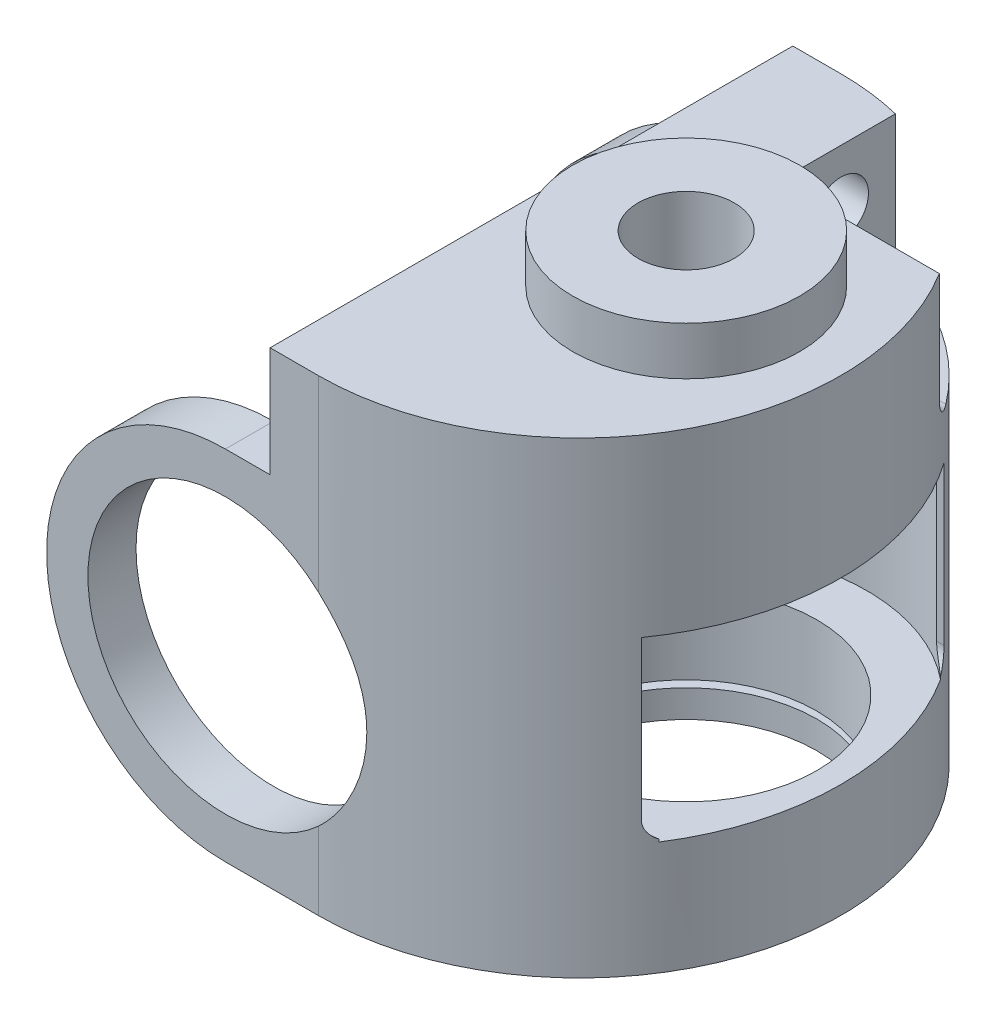
SolidWorks part; units mm, degrees
ref_plane "Plan de face" through (0, 0, 0) normal (0, 0, 1) x (1, 0, 0)
ref_plane "Plan de dessus" through (0, 0, 0) normal (0, 1, 0) x (1, 0, 0)
ref_plane "Plan de droite" through (0, 0, 0) normal (1, 0, 0) x (0, 0, -1)
sketch "Sketch2" plane through (0, 0, 0) normal (0, 1, 0) x (1, 0, 0)
  line L0 (-3.5, -19) -> (-3.5, 19)
  line L1 (-3.5, 19) -> (0, 19)
  line L2 (-3.5, -19) -> (0, -19)
  line L3 (19, 0) -> (19, 16.5672) construction
  arc A0 (0, -19) -> (0, 19) centre (0, 0) ccw
  circle A1 centre (7.75, 0) radius 3.5
  point P7 (-3.5, 0)
  dimension "D1" = 19
  dimension "D3" = 22.5
  dimension "D4" = 11.25
  dimension "D5" = 7
  dimension "D2" = 38
extrude "Boss-Extrude1" add sketch "Sketch2" along normal blind 34
sketch "Sketch19" plane through (0, 34, 0) normal (0, 1, 0) x (1, 0, 0)
  circle A0 centre (7.75, 0) radius 8.25
  circle A1 centre (7.75, 0) radius 3.5
  dimension "D1" = 16.5
  dimension "D2" = 7
extrude "Boss-Extrude3" add sketch "Sketch19" along normal blind 3.5
sketch "Sketch3" plane through (0, 0, 19) normal (0, 0, 1) x (1, 0, 0)
  line L3 (-3.5, 0) -> (-6.75, 0)
  line L4 (-6.75, 26) -> (-3.5, 26)
  line L5 (-3.5, 34) -> (-3.5, 0) construction
  arc A0 (-6.75, 26) -> (-6.75, 0) centre (-6.75, 13) ccw
  line M4 (-3.5, 34) -> (-3.5, 0)
  dimension "D1" = 26
  dimension "D2" = 3.25
extrude "Boss-Extrude2" add sketch "Sketch3" against normal blind 3.5 contours A0 M4 region at (-10.5428, 13, 19)
sketch "Sketch4" plane through (0, 0, 19) normal (0, 0, 1) x (1, 0, 0)
  circle A0 centre (-6.75, 13) radius 10
  dimension "D1" = 20
extrude "Cut-Extrude1" cut sketch "Sketch4" against normal up to surface (3.5 mm away) up to face at (-8.375, 13, 15.5)
pattern_linear "LPattern4" count 2 spacing 34.5 along (0, 0, -1) of "Boss-Extrude2", "Cut-Extrude1"
sketch "Sketch6" plane through (-3.5, 0, 0) normal (1, 0, 0) x (0, 0, -1)
  line L0 (15.5, 0) -> (-15.5, 0) construction
  line L1 (11, 21.25) -> (-11, 21.25)
  line L2 (11, 21.25) -> (11, 9.75)
  line L3 (9.5, 8.25) -> (-9.5, 8.25)
  line L4 (-11, 21.25) -> (-11, 9.75)
  arc A0 (-11, 9.75) -> (-9.5, 8.25) centre (-9.5, 9.75) ccw
  arc A1 (11, 9.75) -> (9.5, 8.25) centre (9.5, 9.75) cw
  point P6 (0, 8.25)
  point P10 (-11, 8.25)
  point P13 (11, 8.25)
  dimension "D4" = 1.5
  dimension "D1" = 8.25
  dimension "D2" = 22
  dimension "D3" = 13
extrude "Cut-Extrude3" cut sketch "Sketch6" along normal through all
sketch "Sketch7" plane through (0, 0, 15.5) normal (0, 0, -1) x (-1, 0, 0)
  circle A3 centre (6.75, 13) radius 13.5
  dimension "D3" = 27
extrude "Cut-Extrude4" cut sketch "Sketch7" along normal blind 4.5 contours A3
pattern_linear "LPattern3" count 2 spacing 26.5 along (0, 0, -1) of "Cut-Extrude4"
sketch "Sketch16" plane through (-3.5, 0, 0) normal (-1, 0, 0) x (0, 0, 1)
  line L0 (19, 34) -> (19, 26) construction
  line L1 (-19, 34) -> (19, 34) construction
  point P0 (11, 31.5)
  dimension "D1" = 8
  dimension "D2" = 2.5
hole_wizard "M2 Tapped Hole1" positions "Sketch16" profile "Sketch15" tap size "M2" standard "ISO"
sketch "Sketch15" plane through (-3.5, 31.5, 11) normal (0, 1, 0) x (0, 0, 1)
  line L0 (0, 0) -> (0, 5.9807)
  line L1 (0, 5.9807) -> (0.8, 5.5)
  line L2 (0.8, 5.5) -> (0.8, 0)
  line L5 (0.8, 0) -> (0, 0)
  line L10 (0, 5.9807) -> (-0.8, 5.5) construction
  line L11 (0, -6.35) -> (0, 107.95) construction
  dimension "Tap Drill Dia." = 1.6
  dimension "Tap Drill Depth" = 5.5
  dimension "Drill Angle" = 118
cosmetic thread "Hole Thread1" parameters "D1"=4.5, "D2"=2
sketch "Sketch17" plane through (-3.5, 0, 0) normal (-1, 0, 0) x (0, 0, 1)
  line L0 (-19, 34) -> (-19, 26) construction
  line L1 (-19, 34) -> (19, 34) construction
  circle A1 centre (-14.5, 30) radius 2
  dimension "D1" = 4
  dimension "D2" = 4.5
  dimension "D3" = 4
extrude "Cut-Extrude5" cut sketch "Sketch17" against normal blind 8
sketch "Sketch18" plane through (4.5, 0, 0) normal (-1, 0, 0) x (0, 0, 1)
  line L0 (-19, 34) -> (-19, 26) construction
  line L1 (-19, 24.5) -> (-11.5, 24.5)
  line L2 (-19, 24.5) -> (-19, 34)
  line L3 (-19, 34) -> (-10, 34)
  line L4 (-10, 26) -> (-10, 34)
  line L5 (-19, 34) -> (19, 34) construction
  arc A2 (-10, 26) -> (-11.5, 24.5) centre (-11.5, 26) cw
  dimension "D1" = 9.5
  dimension "D2" = 9
  dimension "D3" = 1.5
extrude "Cut-Extrude6" cut sketch "Sketch18" against normal up to next
sketch "Sketch20" plane through (0, 21.25, 0) normal (0, -1, 0) x (1, 0, 0)
  circle A0 centre (7.75, 0) radius 9.75
  dimension "D1" = 19.5
extrude "Cut-Extrude7" cut sketch "Sketch20" against normal blind 6.25
sketch "Sketch21" plane through (0, 27.5, 0) normal (0, -1, 0) x (1, 0, 0)
  circle A0 centre (7.75, 0) radius 8.5
  dimension "D1" = 17
extrude "Cut-Extrude8" cut sketch "Sketch21" against normal blind 0.5
sketch "Sketch22" plane through (0, 8.25, 0) normal (0, 1, 0) x (1, 0, 0)
  circle A0 centre (7.75, 0) radius 9.5
  dimension "D1" = 19
extrude "Cut-Extrude9" cut sketch "Sketch22" against normal blind 5.75
sketch "Sketch23" plane through (0, 2.5, 0) normal (0, 1, 0) x (1, 0, 0)
  circle A0 centre (7.75, 0) radius 10.5
  dimension "D1" = 21
extrude "Cut-Extrude10" cut sketch "Sketch23" against normal blind 0.5
sketch "Sketch24" plane through (0, 2, 0) normal (0, 1, 0) x (1, 0, 0)
  circle A0 centre (7.75, 0) radius 9.5
  dimension "D1" = 19
extrude "Cut-Extrude11" cut sketch "Sketch24" against normal blind 2
sketch "Sketch25" plane through (0, 8.25, 0) normal (0, 1, 0) x (1, 0, 0)
  circle A0 centre (7.75, 0) radius 13.15
  dimension "D1" = 26.3
extrude "Cut-Extrude12" cut sketch "Sketch25" along normal blind 13
